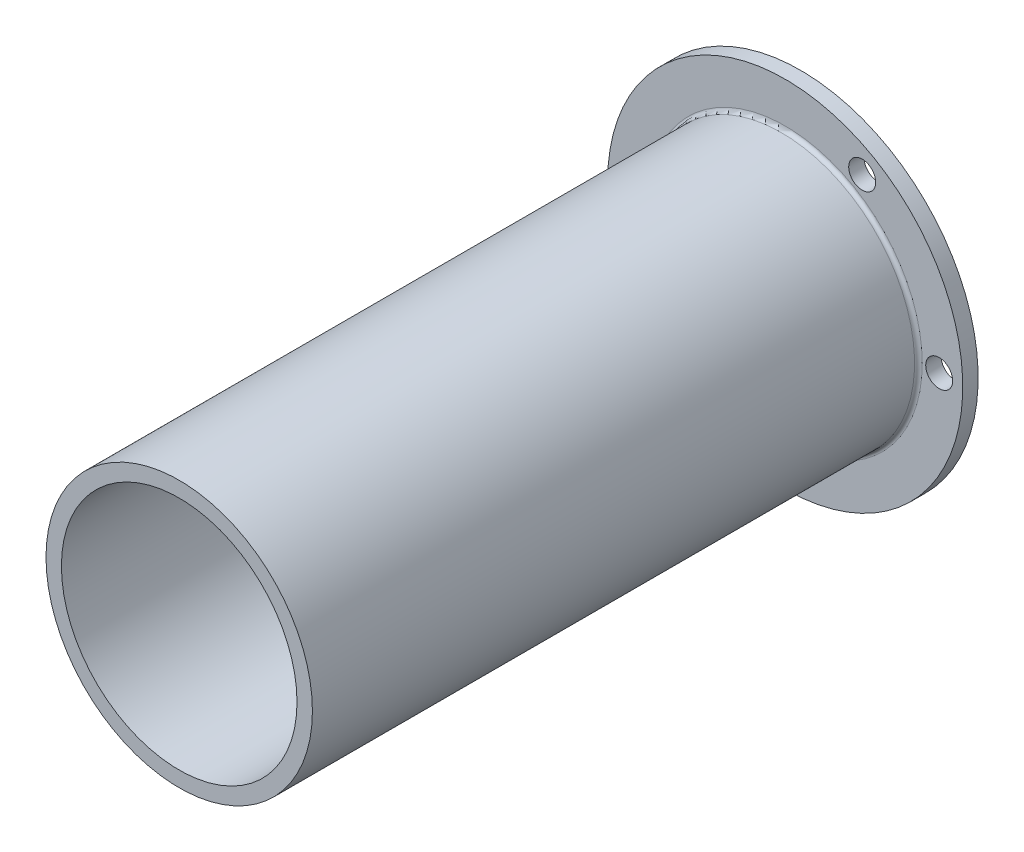
SolidWorks part; units mm, degrees
material "1060 Alloy"
ref_plane "Front Plane" through (0, 0, 0) normal (0, 0, 1) x (1, 0, 0)
ref_plane "Top Plane" through (0, 0, 0) normal (0, 1, 0) x (1, 0, 0)
ref_plane "Right Plane" through (0, 0, 0) normal (1, 0, 0) x (0, 0, -1)
sketch "Sketch1" plane through (0, 0, 0) normal (0, 0, 1) x (1, 0, 0)
  circle A0 centre (0, 0) radius 7.65
  circle A1 centre (0, 0) radius 8.65
  dimension "D1" = 15.3
  dimension "D2" = 17.3
extrude "Boss-Extrude1" add sketch "Sketch1" along normal blind 39.35
sketch "Sketch2" plane through (0, 0, 0) normal (0, 0, -1) x (-1, 0, 0)
  circle A0 centre (0, 0) radius 11.53
  circle A2 centre (0, 0) radius 7.65
  dimension "D1" = 23.06
extrude "Boss-Extrude2" add sketch "Sketch2" along normal blind 1
hole_wizard "Ø2.0mm Dowel Hole1" positions "Sketch10" profile "Sketch11" hole size "Ø2.0" standard "ISO"
sketch "Sketch10" plane through (0, 0, 0) normal (0, 0, 1) x (1, 0, 0)
  point P0 (-10, 0)
  dimension "D1" = 10
sketch "Sketch11" plane through (-10, 0, 0) normal (1, 0, 0) x (0, -1, 0)
  line L0 (0, 0) -> (0, 5.5258)
  line L1 (0, 5.5258) -> (0.875, 5)
  line L2 (0.875, 5) -> (0.875, 0)
  line L5 (0.875, 0) -> (0, 0)
  line L10 (0, 5.5258) -> (-0.875, 5) construction
  line L11 (0, -6.35) -> (0, 107.95) construction
  dimension "Hole Dia." = 1.75
  dimension "Hole Depth" = 5
  dimension "Drill Angle" = 118
pattern_circular "CirPattern1" count 6 over 360 about axis through (0, 0, 0) along (0, 0, -1) skipping 1, 4 of "Ø2.0mm Dowel Hole1"
fillet "Fillet1" radius 0.25 1 edges at (8.65, 0, 0)
